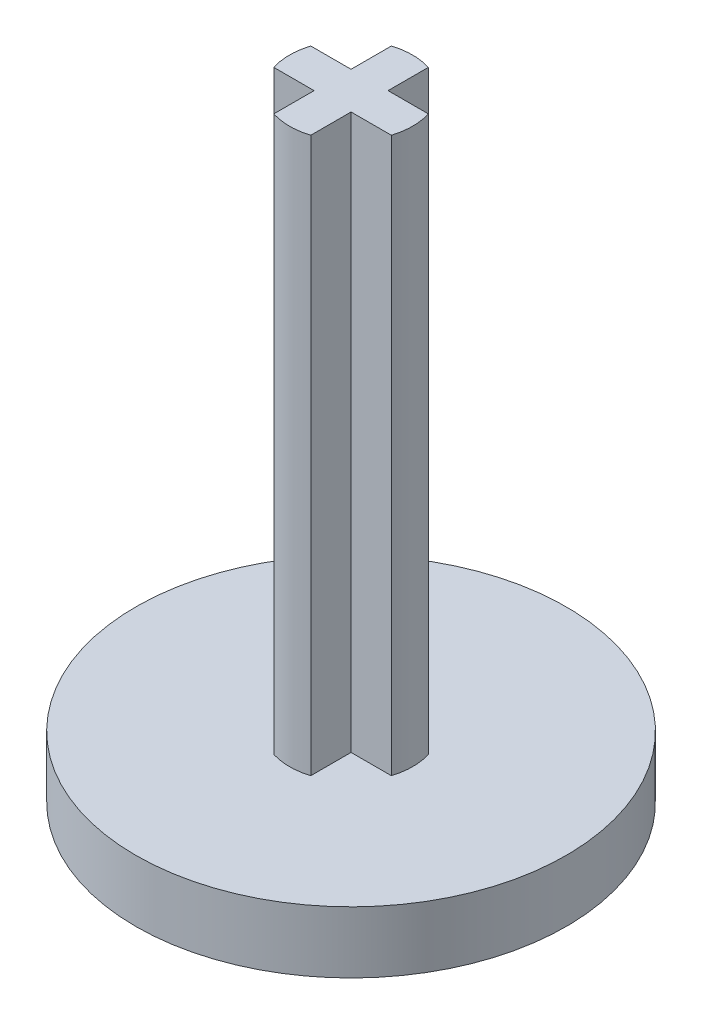
SolidWorks part; units mm, degrees
ref_plane "Front Plane" through (0, 0, 0) normal (0, 0, 1) x (1, 0, 0)
ref_plane "Top Plane" through (0, 0, 0) normal (0, 1, 0) x (1, 0, 0)
ref_plane "Right Plane" through (0, 0, 0) normal (1, 0, 0) x (0, 0, -1)
sketch "Sketch1" plane through (0, 0, 0) normal (0, 1, 0) x (1, 0, 0)
  circle A0 centre (0, 0) radius 17.4625
  dimension "D1" = 34.925
extrude "Boss-Extrude1" add sketch "Sketch1" along normal blind 5
extrude "Boss-Extrude2" add sketch "Sketch1<2>" along normal blind 5 from offset 127 separate body
sketch "Sketch1<2>" plane through (0, 0, 0) normal (0, 1, 0) x (1, 0, 0) same geometry as "Sketch1"
sketch "Sketch2" plane through (0, 5, 0) normal (0, 1, 0) x (1, 0, 0)
  line L2 (-4.7697, -1.5) -> (-1.5, -1.5)
  line L3 (-4.7697, 1.5) -> (-1.5, 1.5)
  line L4 (-1.5, 4.7697) -> (-1.5, 1.5)
  line L5 (1.5, 4.7697) -> (1.5, 1.5)
  line L12 (1.5, 1.5) -> (4.7697, 1.5)
  line L13 (-1.5, -1.5) -> (-1.5, -4.7697)
  line L14 (1.5, -1.5) -> (4.7697, -1.5)
  line L15 (1.5, -1.5) -> (1.5, -4.7697)
  arc A0 (-1.5, -4.7697) -> (1.5, -4.7697) centre (0, 0) ccw
  arc A1 (4.7697, -1.5) -> (4.7697, 1.5) centre (0, 0) ccw
  arc A2 (1.5, 4.7697) -> (-1.5, 4.7697) centre (0, 0) ccw
  arc A3 (-4.7697, 1.5) -> (-4.7697, -1.5) centre (0, 0) ccw
extrude "Boss-Extrude3" add sketch "Sketch2" along normal up to surface (122 mm away) up to face at (0, 127, 17.4625)
sketch "Sketch3" plane through (0, 0, 0) normal (0, 0, 1) x (1, 0, 0)
  line L1 (-17.4625, 132) -> (17.4625, 132)
  line L2 (-17.4625, 132) -> (-17.4625, 50)
  line L3 (-17.4625, 50) -> (17.4625, 50)
  line L4 (17.4625, 132) -> (17.4625, 50)
  line L5 (-17.4625, 132) -> (17.4625, 50) construction
  line L6 (-17.4625, 50) -> (17.4625, 132) construction
  line L7 (17.4625, 0) -> (-17.4625, 0)
  line L8 (17.4625, 0) -> (17.4625, 50)
  line L9 (17.4625, 50) -> (-17.4625, 50)
  line L10 (-17.4625, 0) -> (-17.4625, 50)
  line L11 (17.4625, 0) -> (-17.4625, 50) construction
  line L12 (17.4625, 50) -> (-17.4625, 0) construction
  point P4 (0, 91)
  point P9 (0, 25)
  dimension "D1" = 50
extrude "Cut-Extrude1" cut sketch "Sketch3" against normal through all both and the other way through all contours L4 L1 L2 L3 region at (0, 91, 0)
